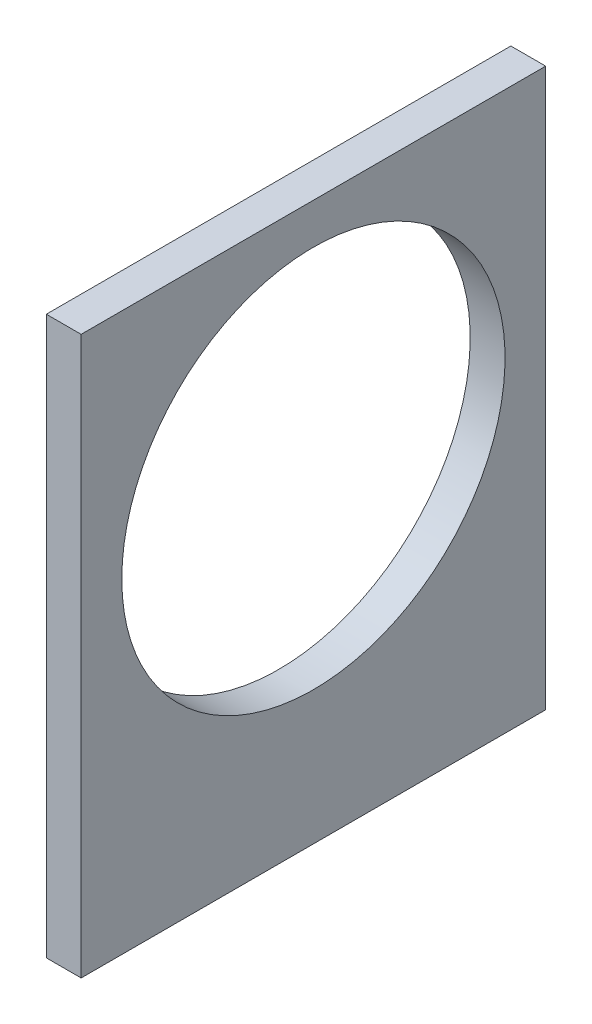
SolidWorks part; units mm, degrees
material "6061-T6 (SS)"
ref_plane "Front Plane" through (0, 0, 0) normal (0, 0, 1) x (1, 0, 0)
ref_plane "Top Plane" through (0, 0, 0) normal (0, 1, 0) x (1, 0, 0)
ref_plane "Right Plane" through (0, 0, 0) normal (1, 0, 0) x (0, 0, -1)
sketch "Sketch4" plane through (0, 0, 0) normal (1, 0, 0) x (0, 0, -1)
  line L1 (31.75, 38.1) -> (-31.75, 38.1)
  line L2 (31.75, 38.1) -> (31.75, -38.1)
  line L3 (31.75, -38.1) -> (-31.75, -38.1)
  line L4 (-31.75, 38.1) -> (-31.75, -38.1)
  line L5 (31.75, 38.1) -> (-31.75, -38.1) construction
  line L6 (31.75, -38.1) -> (-31.75, 38.1) construction
  circle A0 centre (0, 6.35) radius 26.1938
  point P0 (0, 0)
  dimension "D3" = 52.3875
  dimension "D1" = 31.75
  dimension "D2" = 63.5
  dimension "D4" = 76.2
extrude "Boss-Extrude2" add sketch "Sketch4" along normal blind 4.7625
hole_wizard "#6-32 Tapped Hole3" positions "Sketch9" profile "Sketch8" tap size "#6-32" standard "ANSI Inch"
sketch "Sketch9" plane through (0, -38.1, 0) normal (0, -1, 0) x (-1, 0, 0)
  line L0 (-4.7625, -31.75) -> (0, -31.75) construction
  line L1 (-4.7625, 31.75) -> (0, 31.75) construction
  point P0 (-2.3813, -28.575)
  point P2 (-2.3813, 28.575)
  point P9 (0, 0)
  point P10 (-2.3813, -31.75)
  dimension "D1" = 3.175
  dimension "D2" = 3.175
cosmetic thread "Hole Thread5" parameters "D1"=12.7, "D2"=3.5052
cosmetic thread "Hole Thread6" parameters "D1"=12.7, "D2"=3.5052
sketch "Sketch8" plane through (2.3813, -38.1, 28.575) normal (1, 0, 0) x (0, 0, -1)
  line L0 (0, 0) -> (0, 17.4751)
  line L1 (0, 17.4751) -> (1.3525, 16.6624)
  line L2 (1.3525, 16.6624) -> (1.3525, 0)
  line L5 (1.3525, 0) -> (0, 0)
  line L10 (0, 17.4751) -> (-1.3526, 16.6624) construction
  line L11 (0, -6.35) -> (0, 107.95) construction
  dimension "Tap Drill Dia." = 2.7051
  dimension "Tap Drill Depth" = 16.6624
  dimension "Drill Angle" = 118
